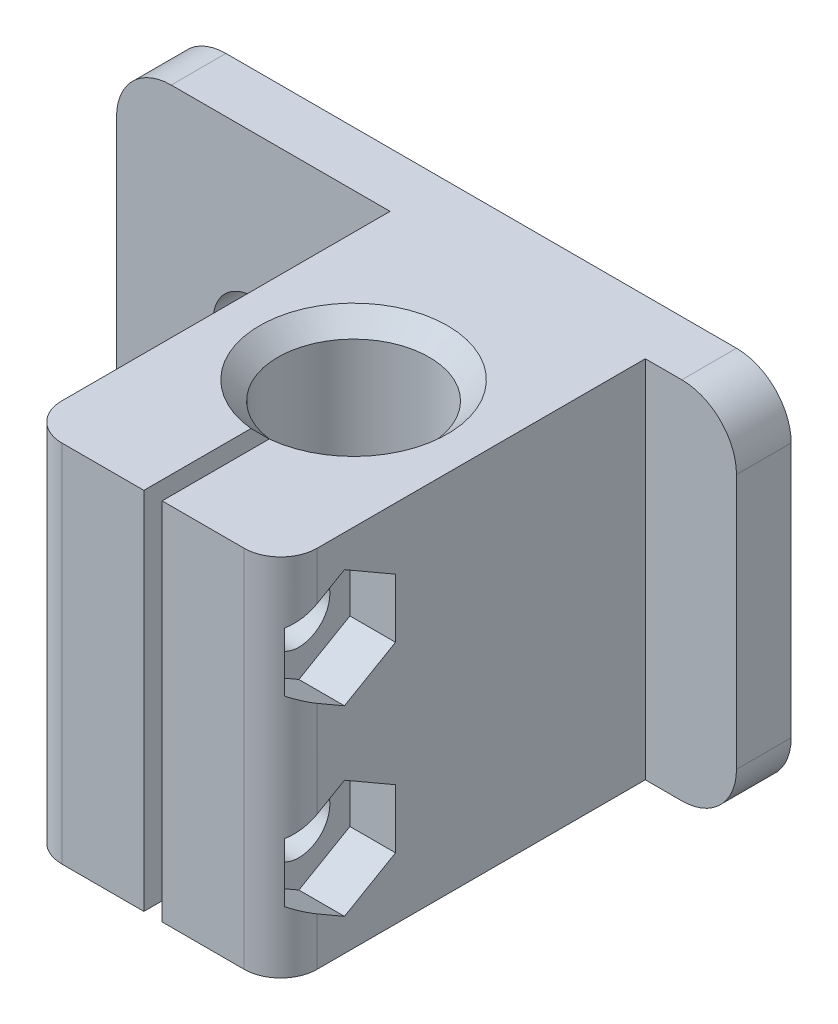
SolidWorks part; units mm, degrees
material "ABS"
ref_plane "Front Plane" through (0, 0, 0) normal (0, 0, 1) x (1, 0, 0)
ref_plane "Top Plane" through (0, 0, 0) normal (0, 1, 0) x (1, 0, 0)
ref_plane "Right Plane" through (0, 0, 0) normal (1, 0, 0) x (0, 0, -1)
sketch "Sketch1" plane through (0, 0, 0) normal (0, 0, 1) x (1, 0, 0)
  line L1 (-17, -10) -> (17, -10)
  line L2 (-17, -10) -> (-17, 10)
  line L3 (-17, 10) -> (17, 10)
  line L4 (17, -10) -> (17, 10)
  line L5 (-17, -10) -> (17, 10) construction
  line L6 (-17, 10) -> (17, -10) construction
  point P0 (0, 0)
  dimension "D1" = 20
  dimension "D2" = 34
extrude "Boss-Extrude1" add sketch "Sketch1" along normal blind 3
fillet "Fillet1" radius 3 4 edges at (17, -10, 1.5) (-17, -10, 1.5) (-17, 10, 1.5) (17, 10, 1.5)
sketch "Sketch2" plane through (0, 0, 3) normal (0, 0, 1) x (1, 0, 0)
  line L0 (14, 10) -> (-14, 10) construction
  line L1 (12, 10) -> (-2, 10)
  line L2 (12, 10) -> (12, -10)
  line L3 (12, -10) -> (-2, -10)
  line L4 (-2, 10) -> (-2, -10)
  line L5 (-14, -10) -> (14, -10) construction
  line L6 (17, -7) -> (17, 7) construction
  dimension "D1" = 14
  dimension "D2" = 5
extrude "Boss-Extrude2" add sketch "Sketch2" along normal blind 20
sketch "Sketch3" plane through (0, 10, 0) normal (0, 1, 0) x (1, 0, 0)
  line L0 (5, -12) -> (5, -23) construction
  line L1 (12, -23) -> (-2, -23) construction
  line L2 (4.5, -16.1198) -> (4.5, -23)
  line L3 (5.5, -16.1198) -> (5.5, -23)
  line L4 (4.5, -23) -> (5.5, -23)
  line L5 (14, 0) -> (-14, 0) construction
  arc A0 (5.5, -16.1198) -> (4.5, -16.1198) centre (5, -12) ccw
  dimension "D1" = 8.3
  dimension "D2" = 12
  dimension "D3" = 1
extrude "Cut-Extrude1" cut sketch "Sketch3" against normal through all
chamfer "Chamfer1" distance 1 angle 45 2 edges at (5, -10, 7.85) (5, 10, 7.85)
sketch "Sketch4" plane through (0, 0, 3) normal (0, 0, 1) x (1, 0, 0)
  line L0 (-2, 10) -> (-14, 10) construction
  line L1 (-17, 7) -> (-17, -7) construction
  circle A0 centre (-9.5, 0) radius 2.2
  point P4 (-8, 10)
  dimension "D1" = 4.4
  dimension "D2" = 10
  dimension "D3" = 7.5
extrude "Cut-Extrude2" cut sketch "Sketch4" against normal through all
sketch "Sketch5" plane through (12, 0, 0) normal (1, 0, 0) x (0, 0, -1)
  line L0 (0, -7) -> (0, 7) construction
  line L1 (-19.5, 5) -> (-19.5, -5) construction
  line L2 (-19.5, 0) -> (-23, 0) construction
  line L3 (-23, -10) -> (-23, 10) construction
  circle A0 centre (-19.5, 5) radius 1.7
  circle A1 centre (-19.5, -5) radius 1.7
  dimension "D1" = 3.4
  dimension "D2" = 10
  dimension "D3" = 19.5
extrude "Cut-Extrude3" cut sketch "Sketch5" against normal through all
fillet "Fillet2" radius 2 2 edges at (12, 0, 23) (-2, 0, 23)
sketch "Sketch6" plane through (12, 0, 0) normal (1, 0, 0) x (0, 0, -1)
  line L1 (-16.7, 3.3834) -> (-16.7, 6.6166)
  line L2 (-16.7, 6.6166) -> (-19.5, 8.2332)
  line L3 (-19.5, 8.2332) -> (-22.3, 6.6166)
  line L4 (-22.3, 6.6166) -> (-22.3, 3.3834)
  line L5 (-22.3, 3.3834) -> (-19.5, 1.7668)
  line L6 (-19.5, 1.7668) -> (-16.7, 3.3834)
  line L7 (-16.7, -3.3834) -> (-19.5, -1.7668)
  line L8 (-19.5, -1.7668) -> (-22.3, -3.3834)
  line L9 (-22.3, -3.3834) -> (-22.3, -6.6166)
  line L10 (-22.3, -6.6166) -> (-19.5, -8.2332)
  line L11 (-19.5, -8.2332) -> (-16.7, -6.6166)
  line L12 (-16.7, -6.6166) -> (-16.7, -3.3834)
  circle A0 centre (-19.5, 5) radius 2.8 construction
  circle A1 centre (-19.5, -5) radius 2.8 construction
  dimension "D1" = 5.6
extrude "Cut-Extrude4" cut sketch "Sketch6" against normal blind 2.5
sketch "Sketch7" plane through (-2, 0, 0) normal (-1, 0, 0) x (0, 0, 1)
  circle A0 centre (19.5, 5) radius 2.75
  circle A1 centre (19.5, -5) radius 2.75
  dimension "D1" = 5.5
extrude "Cut-Extrude5" cut sketch "Sketch7" against normal blind 3
